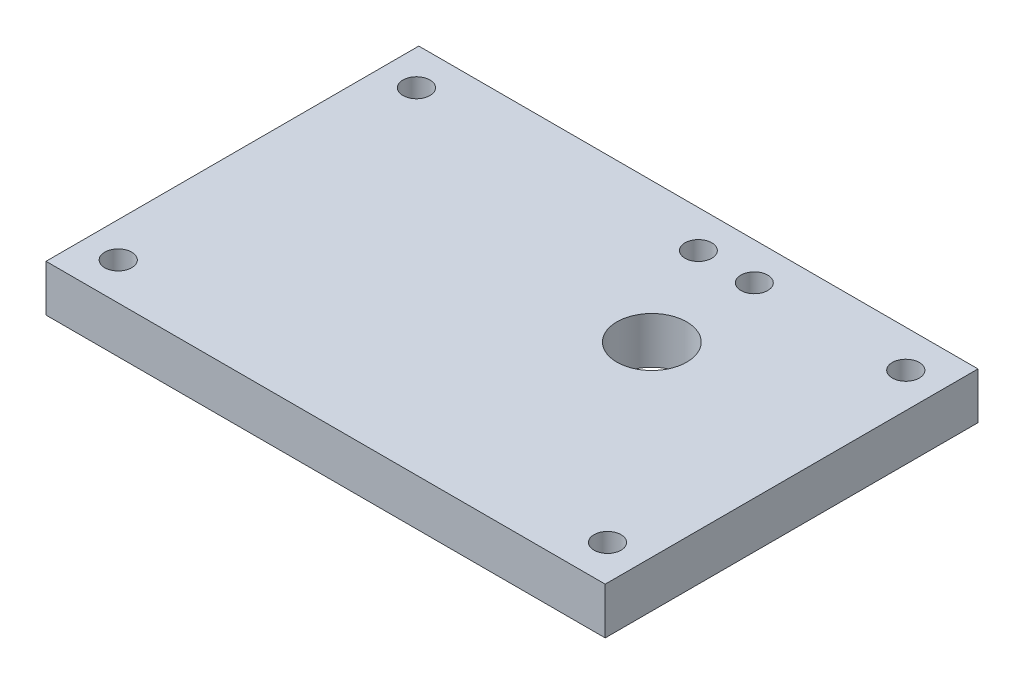
SolidWorks part; units mm, degrees
ref_plane "Front Plane" through (0, 0, 0) normal (0, 0, 1) x (1, 0, 0)
ref_plane "Top Plane" through (0, 0, 0) normal (0, 1, 0) x (1, 0, 0)
ref_plane "Right Plane" through (0, 0, 0) normal (1, 0, 0) x (0, 0, -1)
sketch "Sketch1" plane through (0, 0, 0) normal (0, 1, 0) x (1, 0, 0)
  line L1 (-38.1, 25.4) -> (38.1, 25.4)
  line L2 (-38.1, 25.4) -> (-38.1, -25.4)
  line L3 (-38.1, -25.4) -> (38.1, -25.4)
  line L4 (38.1, 25.4) -> (38.1, -25.4)
  line L5 (-38.1, 25.4) -> (38.1, -25.4) construction
  line L6 (-38.1, -25.4) -> (38.1, 25.4) construction
  point P0 (0, 0)
  dimension "D1" = 50.8
  dimension "D2" = 76.2
extrude "Boss-Extrude1" add sketch "Sketch1" along normal blind 6.35
sketch "Sketch2" plane through (0, 6.35, 0) normal (0, 1, 0) x (1, 0, 0)
  line L0 (-38.1, 25.4) -> (-38.1, -25.4) construction
  line L1 (38.1, 25.4) -> (-38.1, 25.4) construction
  line L2 (-38.1, -25.4) -> (38.1, -25.4) construction
  line L3 (38.1, -25.4) -> (38.1, 25.4) construction
  circle A0 centre (-33.3375, 20.32) radius 1.8415
  circle A1 centre (-33.3375, -20.32) radius 1.8415
  circle A2 centre (33.3375, -20.32) radius 1.8415
  circle A3 centre (33.3375, 20.32) radius 1.8415
  dimension "D3" = 3.683
  dimension "D1" = 4.7625
  dimension "D2" = 5.08
  dimension "D4" = 5.08
  dimension "D5" = 4.7625
extrude "Cut-Extrude1" cut sketch "Sketch2" against normal through all from offset 0
sketch "Sketch3" plane through (0, 6.35, 0) normal (0, 1, 0) x (1, 0, 0)
  line L0 (38.1, 25.4) -> (-38.1, 25.4) construction
  line L1 (38.1, -25.4) -> (38.1, 25.4) construction
  circle A0 centre (12.7, 6.35) radius 4.7625
  circle A1 centre (5.08, 20.32) radius 1.8288
  circle A2 centre (12.7, 20.32) radius 1.8288
  dimension "D4" = 9.525
  dimension "D7" = 3.6576
  dimension "D1" = 5.08
  dimension "D2" = 19.05
  dimension "D3" = 25.4
  dimension "D5" = 7.62
  dimension "D6" = 33.02
extrude "Cut-Extrude2" cut sketch "Sketch3" against normal through all contours A0 | A1 | A2 region at (12.7, 6.35, -6.35)
